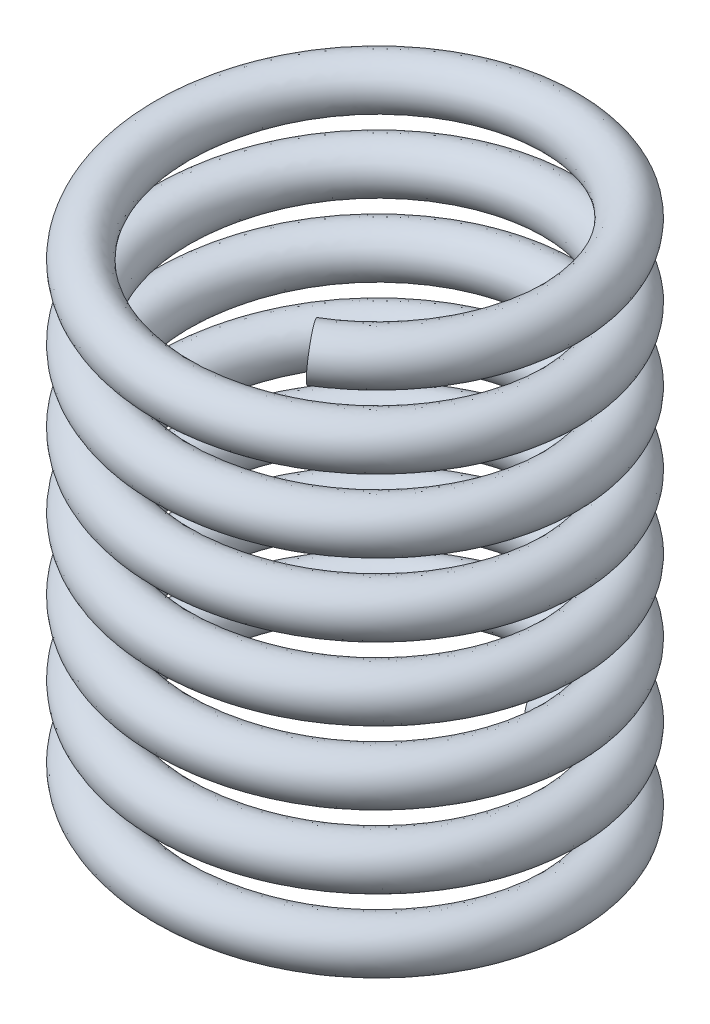
SolidWorks part; units mm, degrees
note: '?' marks a value the reader was unsure of.
material "Plain Carbon Steel"
ref_plane "Front Plane" through (0, 0, 0) normal (0, 0, 1) x (1, 0, 0)
ref_plane "Top Plane" through (0, 0, 0) normal (0, 1, 0) x (1, 0, 0)
ref_plane "Right Plane" through (0, 0, 0) normal (1, 0, 0) x (0, 0, -1)
ref_axis "Axis1" through (0, 55, 0) along (0, -1, 0)?
sketch "Sketch1" plane through (0, 0, 0) normal (0, 1, 0) x (1, 0, 0)
  line L0 (0, -55) -> (0, 55) construction
  circle A0 centre (0, 0) radius 4
  point P5 (0, 0)
  dimension "D1" = 8
curve "Helix/Spiral1" pitch 1.5 height 11.1 turns 7.4
ref_plane "Plane1" through (2.3511, 11.1, 3.2361) normal (-0.8076, 0.0596, 0.5867) x (-0.2215, -0.9527, -0.2082)
sketch "Sketch2" plane through (2.3511, 11.1, 3.2361) normal (-0.8076, 0.0596, 0.5867) x (-0.2215, -0.9527, -0.2082)
  circle A0 centre (0, 0) radius 0.5
  point P2 (0, 0)
  point P3 (0, 0)
  dimension "D1" = 1
sweep "Sweep2" add profiles "Sketch2" path "Helix/Spiral1"
